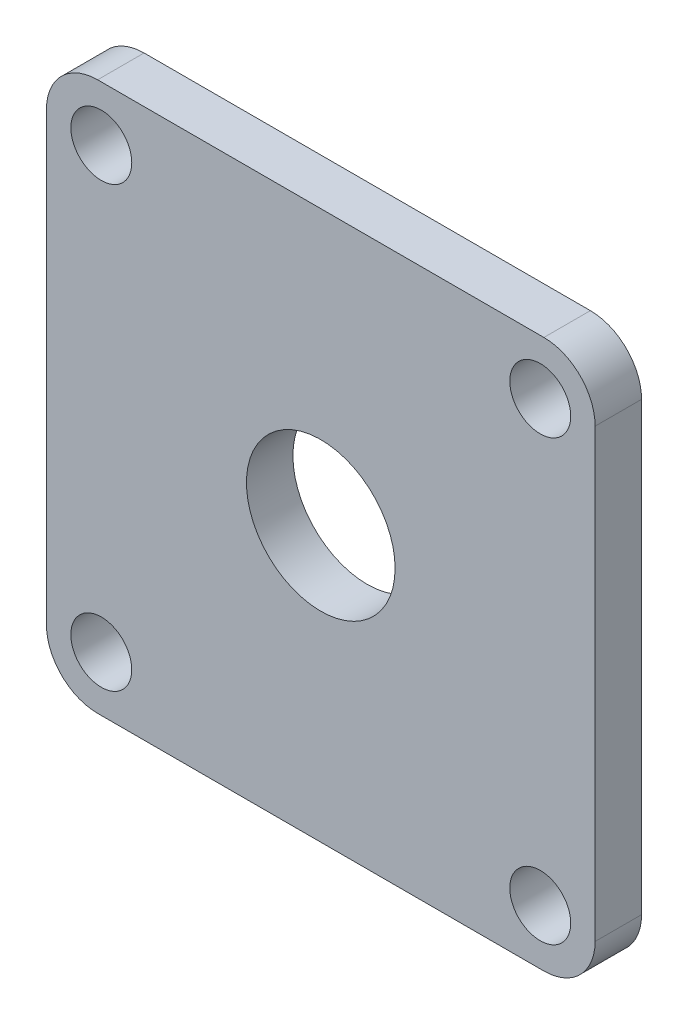
SolidWorks part; units mm, degrees
ref_plane "Front" through (0, 0, 0) normal (0, 0, 1) x (1, 0, 0)
ref_plane "Top" through (0, 0, 0) normal (0, 1, 0) x (1, 0, 0)
ref_plane "Right" through (0, 0, 0) normal (1, 0, 0) x (0, 0, -1)
sketch "Sketch1" plane through (0, 0, 0) normal (0, 0, 1) x (1, 0, 0)
  line L1 (-37.5, -37.5) -> (37.5, -37.5)
  line L2 (-37.5, -37.5) -> (-37.5, 37.5)
  line L3 (-37.5, 37.5) -> (37.5, 37.5)
  line L4 (37.5, -37.5) -> (37.5, 37.5)
  line L5 (-37.5, -37.5) -> (37.5, 37.5) construction
  line L6 (-37.5, 37.5) -> (37.5, -37.5) construction
  point P0 (0, 0)
  dimension "D1" = 75
  dimension "D2" = 75
extrude "Boss-Extrude1" add sketch "Sketch1" along normal blind 6.35
fillet "Fillet1" radius 7 4 edges at (-37.5, -37.5, 3.175) (37.5, -37.5, 3.175) (-37.5, 37.5, 3.175) (37.5, 37.5, 3.175)
sketch "Sketch2" plane through (0, 0, 6.35) normal (0, 0, 1) x (1, 0, 0)
  circle A0 centre (0, 0) radius 10.16
  dimension "D1" = 20.32
extrude "Cut-Extrude1" cut sketch "Sketch2" against normal up to next
sketch "Sketch3" plane through (0, 0, 6.35) normal (0, 0, 1) x (1, 0, 0)
  line L0 (30.5, 37.5) -> (-30.5, 37.5) construction
  line L1 (-37.5, 30.5) -> (-37.5, -30.5) construction
  circle A0 centre (-30, 30) radius 4.165
  dimension "D1" = 8.33
  dimension "D2" = 7.5
  dimension "D3" = 7.5
extrude "Cut-Extrude2" cut sketch "Sketch3" against normal up to next
pattern_circular "CirPattern1" count 4 over 360 about axis through (0, 0, -0.001) along (0, 0, 1) of "Cut-Extrude2" reverse direction yes
